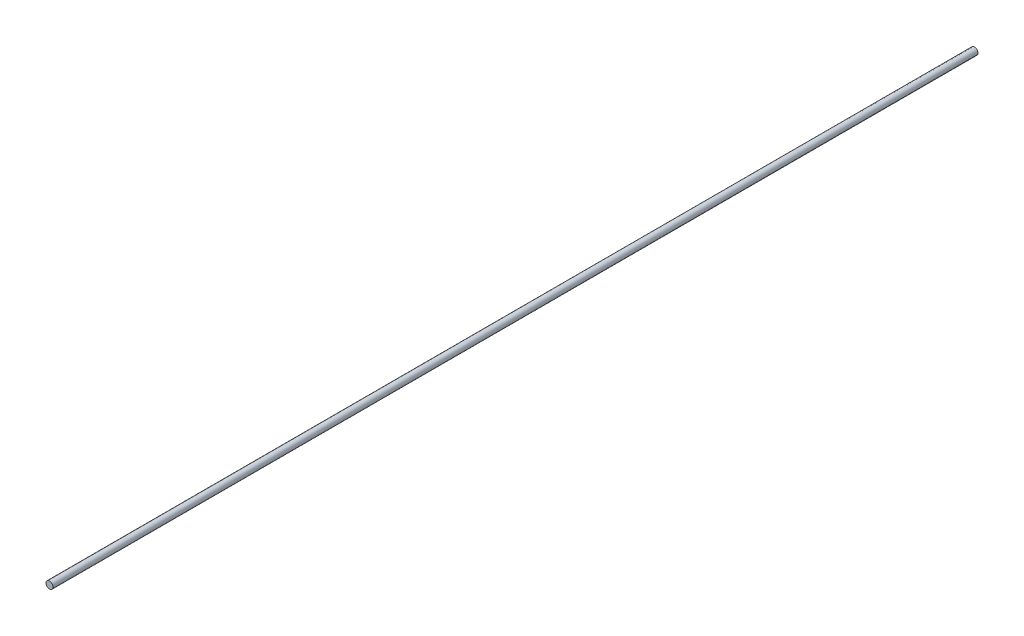
SolidWorks part; units mm, degrees
ref_plane "Front Plane" through (0, 0, 0) normal (0, 0, 1) x (1, 0, 0)
ref_plane "Top Plane" through (0, 0, 0) normal (0, 1, 0) x (1, 0, 0)
ref_plane "Right Plane" through (0, 0, 0) normal (1, 0, 0) x (0, 0, -1)
sketch "Sketch1" plane through (0, 0, 0) normal (0, 0, 1) x (1, 0, 0)
  circle A0 centre (0, 0) radius 2.5
extrude "Rod" add sketch "Sketch1" along normal blind 663
